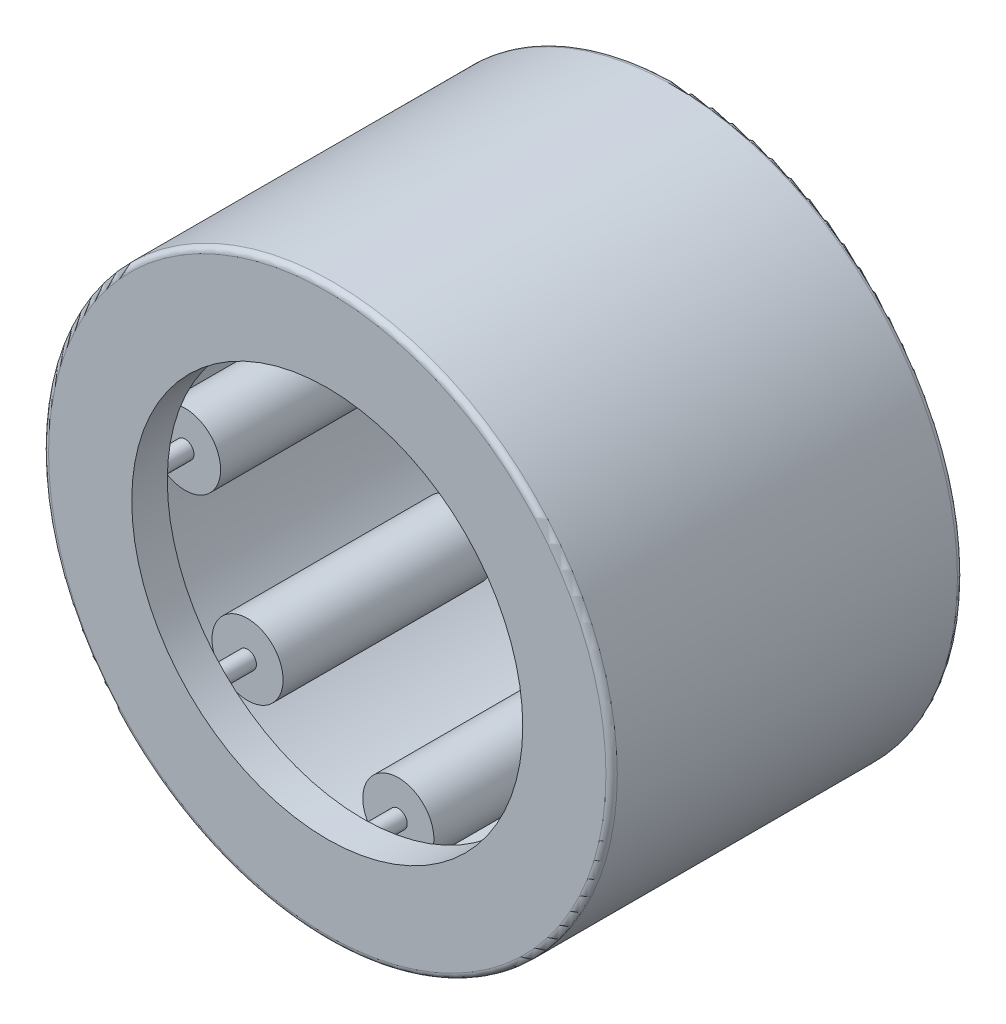
SolidWorks part; units mm, degrees
ref_plane "Front Plane" through (0, 0, 0) normal (0, 0, 1) x (1, 0, 0)
ref_plane "Top Plane" through (0, 0, 0) normal (0, 1, 0) x (1, 0, 0)
ref_plane "Right Plane" through (0, 0, 0) normal (1, 0, 0) x (0, 0, -1)
sketch "Sketch1" plane through (0, 0, 0) normal (1, 0, 0) x (0, 0, -1)
  line L0 (-3.9243, 0) -> (3.9243, 0) construction
  line L1 (0, 0) -> (0, 6.35) construction
  line L2 (-3.9243, 0) -> (-3.9243, 6.35) construction
  line L3 (-3.9243, 6.35) -> (3.9243, 6.35)
  line L4 (3.9243, 6.35) -> (3.9243, 0) construction
  line L5 (3.9243, 0) -> (3.1306, 0) construction
  line L6 (3.1306, 0) -> (3.1305, 5.5562) construction
  line L7 (3.1305, 5.5562) -> (-3.1305, 5.5562)
  line L8 (-3.1305, 5.5562) -> (-3.1306, 0) construction
  line L9 (-3.1306, 0) -> (-3.9243, 0) construction
  line L10 (-3.9243, 6.35) -> (-3.9243, 4.3656)
  line L11 (-3.9243, 4.3656) -> (-3.1306, 4.3656)
  line L12 (-3.1306, 4.3656) -> (-3.1305, 5.5562)
  line L13 (3.1305, 6.35) -> (3.1305, 5.5562) construction
  line L14 (3.1305, 5.5562) -> (3.1306, 4.3656)
  line L15 (3.1306, 4.3656) -> (3.9243, 4.3656)
  line L16 (3.9243, 4.3656) -> (3.9243, 6.35)
  line L17 (3.1305, 5.5562) -> (3.1306, 4.7625) construction
  line L18 (3.1306, 4.7625) -> (3.1306, 3.9687) construction
  point P5 (0, 3.9687)
  dimension "Width" = 7.8486
  dimension "OD" = 12.7
  dimension "Shaft Dia" = 7.9375
revolve "Revolve1" add sketch "Sketch1" angle 360 about L0
sketch "Sketch2" plane through (0, 0, 0) normal (1, 0, 0) x (0, 0, -1)
  line L0 (3.1305, 5.5562) -> (-3.1305, 5.5562) construction
  line L1 (-2.3368, 4.7625) -> (2.3368, 4.7625) construction
  line L2 (-2.3368, 4.7625) -> (-2.3368, 5.5562) construction
  line L3 (-2.3368, 5.5562) -> (2.3368, 5.5562)
  line L4 (2.3368, 4.7625) -> (2.3368, 5.5562) construction
  line L5 (3.1306, 4.3656) -> (3.9243, 4.3656) construction
  line L6 (-3.1306, 4.7625) -> (-2.3368, 4.7625) construction
  line L7 (2.3368, 4.7625) -> (3.1306, 4.7625) construction
  line L8 (-3.9243, 4.3656) -> (-3.1306, 4.3656) construction
  line L9 (-2.3368, 4.9609) -> (-2.3368, 4.5641) construction
  line L10 (-3.1306, 4.7625) -> (-3.1306, 4.3656) construction
  line L11 (-2.3368, 5.5562) -> (-2.3368, 4.9609)
  line L12 (2.3368, 5.5562) -> (2.3368, 4.9609)
  line L13 (2.3368, 4.9609) -> (-2.3368, 4.9609)
  line L14 (0, 5.5563) -> (0, 3.9687) construction
  line L15 (-3.1306, 4.3656) -> (-3.1306, 5.5562) construction
  line L16 (-2.3368, 4.5641) -> (-3.1306, 4.5641) construction
  line L17 (0, 0) -> (3.9243, 0) construction
  line L31 (3.9243, -6.35) -> (3.9243, 6.35) construction
  point P16 (0, 4.7625)
revolve "Revolve2" add sketch "Sketch2" angle 360 about L1
sketch "Sketch3" plane through (0, 0, 0) normal (1, 0, 0) x (0, 0, -1)
  line L0 (3.1305, 5.5562) -> (3.1305, 4.3656) construction
  line L1 (-3.1306, 4.7625) -> (3.1305, 4.7625)
  line L2 (-3.1306, 4.7625) -> (-3.1306, 4.9609)
  line L3 (-3.1306, 4.9609) -> (3.1305, 4.9609)
  line L4 (3.1305, 4.7625) -> (3.1305, 4.9609)
  line L5 (0, 0) -> (3.9243, 0) construction
  line L6 (3.9243, -6.35) -> (3.9243, 6.35) construction
revolve "Revolve3" add sketch "Sketch3" angle 360 about L1
ref_axis "Axis1" through (0, 0, -3.9243) along (0, 0, 1)
pattern_circular "CirPattern1" count 8 every 45 about axis through (0, 0, -3.9243) along (0, 0, 1) of bodies 166 167
fillet "Fillet1" radius 0.127 2 edges at (6.35, 0, -3.9243) (6.35, 0, 3.9243)
sketch "Sketch4" plane through (0, 0, 0) normal (1, 0, 0) x (0, 0, -1)
  line L1 (3.7973, 3.9687) -> (2.3368, 3.9687)
  line L2 (3.7973, 3.9687) -> (3.7973, 4.3656)
  line L3 (3.7973, 4.3656) -> (2.3368, 4.3656)
  line L4 (2.3368, 3.9687) -> (2.3368, 4.3656)
  line L5 (-3.9243, 4.3656) -> (-3.1306, 4.3656) construction
  line L6 (3.7973, -6.35) -> (3.7973, 6.35) construction
  line L7 (2.3368, 5.5562) -> (2.3368, 4.9609) construction
revolve "Revolve4" [suppressed] add sketch "Sketch4" angle 360 about L0
sketch "Sketch5" plane through (0, 0, 0) normal (1, 0, 0) x (0, 0, -1)
  line L0 (-3.7973, 6.35) -> (-3.7973, -6.35) construction
  line L1 (-2.3368, 3.9687) -> (-3.7973, 3.9687)
  line L2 (-2.3368, 3.9687) -> (-2.3368, 4.3656)
  line L3 (-2.3368, 4.3656) -> (-3.7973, 4.3656)
  line L4 (-3.7973, 3.9687) -> (-3.7973, 4.3656)
  line L6 (-2.3368, 5.5562) -> (-2.3368, 4.9609) construction
  line L7 (-3.9243, 4.3656) -> (-3.1306, 4.3656) construction
revolve "Revolve5" [suppressed] add sketch "Sketch5" angle 360 about L0
sketch "Front View" plane through (0, 0, 0) normal (0, 0, 1) x (1, 0, 0)
  circle A0 centre (0, 0) radius 3.9688 construction
  circle A1 centre (0, 0) radius 6.35 construction
  dimension "OD" = 12.7
  dimension "ID" = 7.9375
sketch "Right View" plane through (0, 0, 0) normal (1, 0, 0) x (0, 0, -1)
  line L0 (-3.9243, 6.35) -> (3.9243, 6.35) construction
  dimension "Width" = 7.8486
ref_axis "Center Axis 1" through (0, 0, -3.7973) along (0, 0, 1)
ref_plane "Contact Plane 1" through (0, 0, 3.9243) normal (0, 0, 1) x (1, 0, 0)
ref_plane "Contact Plane 2" through (0, 0, -3.9243) normal (0, 0, -1) x (-1, 0, 0)
equation "\"Rollers@CirPattern1\" = \"OD@Sketch1\"*16"
equation "\"D1@Fillet1\" = \"OD@Sketch1\"*.01"
equation "\"Angle@CirPattern1\"= 360 / \"Rollers@CirPattern1\""
equation "\"OD@Front View\"=\"OD@Sketch1\""
equation "\"ID@Front View\"=\"Shaft Dia@Sketch1\""
equation "\"Width@Right View\"=\"Width@Sketch1\""
